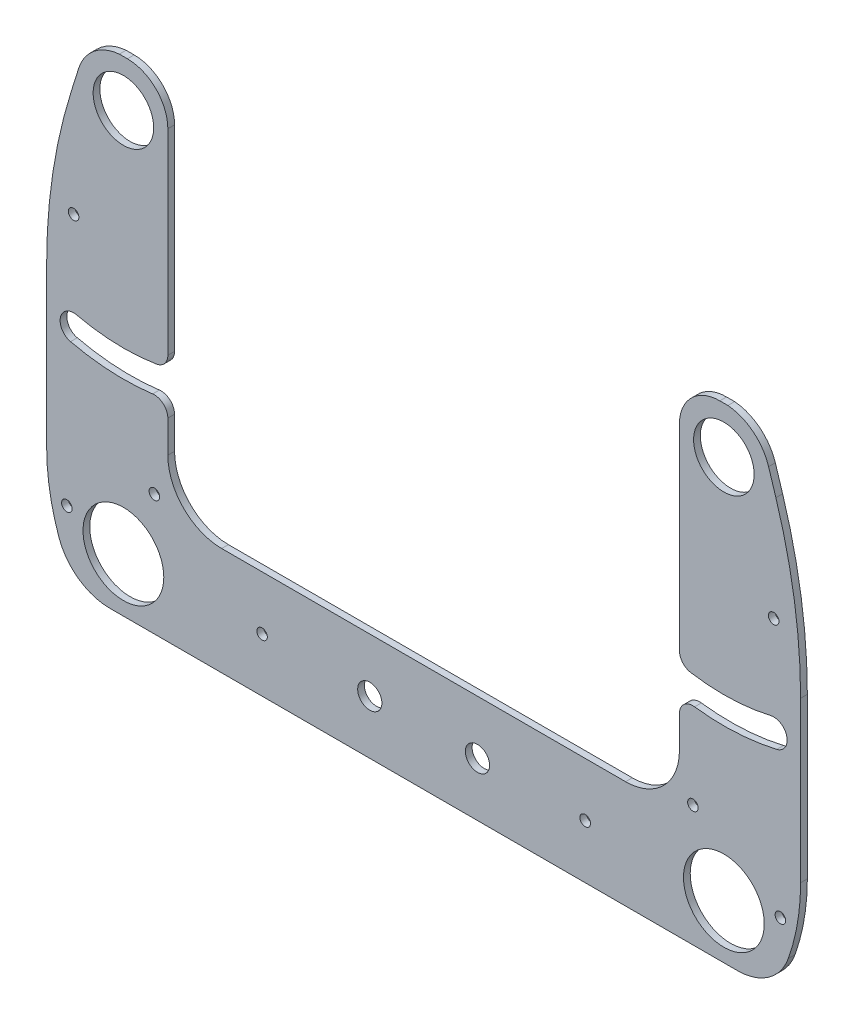
SolidWorks part; units mm, degrees
material "6061 Alloy"
ref_plane "Front Plane" through (0, 0, 0) normal (0, 0, 1) x (1, 0, 0)
ref_plane "Top Plane" through (0, 0, 0) normal (0, 1, 0) x (1, 0, 0)
ref_plane "Right Plane" through (0, 0, 0) normal (1, 0, 0) x (0, 0, -1)
sketch "Sketch1" plane through (0, 0, 0) normal (0, 0, 1) x (1, 0, 0)
  line L5 (120.65, -152.4) -> (120.65, -6.35)
  line L6 (127, 0) -> (171.45, 0) construction
  line L7 (177.8, -6.35) -> (177.8, -222.25)
  line L10 (0, -206.2199) -> (0, -63.6275) construction
  line L11 (-54.9244, 0) -> (300.6756, 0) construction
  line L13 (12.7, -177.8) -> (95.25, -177.8)
  line L14 (12.7, -228.6) -> (171.45, -228.6)
  line L15 (141.605, -22.0269) -> (141.605, -80.9091) construction
  line L16 (141.605, -22.0269) -> (141.605, -123.6269) construction
  line L19 (-141.605, -19.05) -> (-141.605, -77.9322) construction
  line L20 (141.605, -22.0269) -> (141.605, -203.2) construction
  line L22 (-120.65, -152.4) -> (-120.65, -6.35)
  line L23 (-12.7, -177.8) -> (-95.25, -177.8)
  line L24 (-12.7, -228.6) -> (-171.45, -228.6)
  line L25 (-177.8, -6.35) -> (-177.8, -222.25)
  line L26 (-12.7, -177.8) -> (12.7, -177.8)
  line L27 (-12.7, -228.6) -> (12.7, -228.6)
  line L28 (-177.8, -6.35) -> (-177.8, 6.35)
  line L29 (-165.1, 19.05) -> (-133.35, 19.05)
  line L30 (-120.65, 6.35) -> (-120.65, -6.35)
  line L31 (120.65, 6.35) -> (120.65, -6.35)
  line L32 (177.8, -6.35) -> (177.8, 6.35)
  line L33 (165.1, 19.05) -> (133.35, 19.05)
  arc A0 (95.25, -177.8) -> (120.65, -152.4) centre (95.25, -152.4) ccw
  arc A4 (120.65, -6.35) -> (127, 0) centre (127, -6.35) cw construction
  circle A8 centre (141.605, -22.0269) radius 14.2875
  circle A9 centre (141.605, -22.0269) radius 38.1 construction
  arc A10 (177.8, -6.35) -> (171.45, 0) centre (171.45, -6.35) ccw construction
  arc A11 (171.45, -228.6) -> (177.8, -222.25) centre (171.45, -222.25) ccw
  arc A14 (141.605, -79.1769) -> (120.9214, -75.3027) centre (141.605, -22.0269) ccw construction
  arc A15 (-141.605, -79.1769) -> (-120.9214, -75.3027) centre (-141.605, -22.0269) cw construction
  circle A16 centre (-141.605, -22.0269) radius 38.1 construction
  circle A17 centre (-141.605, -22.0269) radius 14.2875
  arc A19 (-95.25, -177.8) -> (-120.65, -152.4) centre (-95.25, -152.4) cw
  circle A20 centre (141.605, -123.6269) radius 38.1 construction
  circle A21 centre (-141.605, -123.6269) radius 38.1 construction
  arc A23 (-171.45, -228.6) -> (-177.8, -222.25) centre (-171.45, -222.25) cw
  circle A24 centre (-141.605, -203.2) radius 19.05
  circle A37 centre (141.605, -203.2) radius 19.05
  circle A39 centre (-76.2, -203.2) radius 2.4892
  circle A40 centre (76.2, -203.2) radius 2.4892
  circle A42 centre (-25.4, -203.2) radius 5.715
  arc A44 (-133.35, 19.05) -> (-120.65, 6.35) centre (-133.35, 6.35) cw
  arc A45 (-177.8, 6.35) -> (-165.1, 19.05) centre (-165.1, 6.35) cw
  arc A46 (133.35, 19.05) -> (120.65, 6.35) centre (133.35, 6.35) ccw
  arc A47 (177.8, 6.35) -> (165.1, 19.05) centre (165.1, 6.35) ccw
  circle A50 centre (-149.225, 6.35) radius 2.4892
  circle A53 centre (149.225, 6.35) radius 2.4892
  circle A54 centre (-168.275, -196.85) radius 2.4892
  circle A56 centre (168.275, -196.85) radius 2.4892
  circle A58 centre (-165.1, -76.2) radius 2.4892
  circle A59 centre (165.1, -76.2) radius 2.4892
  circle A60 centre (-127, -171.45) radius 2.4892
  circle A61 centre (127, -171.45) radius 2.4892
  circle A62 centre (25.4, -203.2) radius 5.715
  point P2 (177.8, -44.45)
  point P18 (177.8, 0)
  point P23 (177.8, -228.6)
  point P24 (177.8, -228.6)
  point P31 (177.8, 0)
  point P48 (-177.8, 0)
  point P49 (-177.8, -228.6)
  point P51 (-177.8, -44.45)
  point P78 (-141.605, -203.2)
  dimension "D6" = 25.4
  dimension "D7" = 6.35
  dimension "D8" = 6.35
  dimension "D9" = 177.8
  dimension "D10" = 28.575
  dimension "D12" = 76.2
  dimension "D13" = 57.15
  dimension "D15" = 38.1
  dimension "D18" = 76.2
  dimension "D21" = 4.9784
  dimension "D29" = 9.525
  dimension "D32" = 4.9784
  dimension "D35" = 11.43
  dimension "D40" = 12.7
  dimension "D43" = 4.9784
  dimension "D45" = 12.7
  dimension "D30" = 4.9784
  dimension "D41" = 4.9784
  dimension "D22" = 6.35
  dimension "D2" = 120.65
  dimension "D3" = 177.8
  dimension "D4" = 228.6
  dimension "D5" = 177.8
  dimension "D11" = 20.955
  dimension "`" = 22.0269
  dimension "D14" = 57.15
  dimension "D16" = 184.15
  dimension "D17" = 101.6
  dimension "D19" = 25.4
  dimension "D20" = 101.6
  dimension "D23" = 57.15
  dimension "D25" = 25.4
  dimension "D26" = 31.75
  dimension "D27" = 25.4
  dimension "D28" = 25.4
  dimension "D31" = 25.4
  dimension "D33" = 12.7
  dimension "D34" = 25.4
  dimension "D39" = 19.05
  dimension "D44" = 28.575
  dimension "D24" = 95.25
extrude "Boss-Extrude3" add sketch "Sketch1" along normal blind 3.175
sketch "Sketch2" plane through (0, 0, 3.175) normal (0, 0, 1) x (1, 0, 0)
  line L0 (177.8, -222.25) -> (177.8, 6.35) construction
  line L1 (-177.8, 19.05) -> (177.8, 19.05)
  line L2 (-177.8, 19.05) -> (-177.8, 0)
  line L3 (-177.8, 0) -> (177.8, 0)
  line L4 (177.8, 19.05) -> (177.8, 0)
  line L5 (-177.8, 6.35) -> (-177.8, -222.25) construction
  line L7 (-133.35, 19.05) -> (-165.1, 19.05) construction
  dimension "D1" = 19.05
extrude "Cut-Extrude1" cut sketch "Sketch2" against normal through all
fillet "Fillet1" radius 19.05 4 edges at (177.8, 0, 1.5875) (120.65, 0, 1.5875) (-120.65, 0, 1.5875) (-177.8, 0, 1.5875)
sketch "Sketch3" plane through (0, 0, 3.175) normal (0, 0, 1) x (1, 0, 0)
  line L2 (-177.8, -19.05) -> (-177.8, -222.25) construction
  line L3 (-158.75, 0) -> (-139.7, 0) construction
  line L4 (-177.8, -63.5) -> (-177.8, 0)
  line L5 (-177.8, 0) -> (-139.7, 0)
  line L6 (-177.8, -63.5) -> (-162.6988, -15.4039)
  arc A3 (-139.7, 0) -> (-162.6988, -15.4039) centre (-141.605, -22.0269) ccw
  arc M14 (-158.75, 0) -> (-177.8, -19.05) centre (-158.75, -19.05) ccw
  line M15 (-177.8, -19.05) -> (-177.8, -222.25)
  dimension "D1" = 63.5
extrude "Cut-Extrude2" cut sketch "Sketch3" against normal through all contours A3 L5 M14 M15 | L5 L4 M14 region at (-169.5998, -21.9282, 3.175) region at (-173.5448, -4.2552, 3.175)
ref_plane "Plane1" through (0, 0, 0) normal (-1, 0, 0) x (0, 0, 1)
mirror "Mirror1" about plane through (0, 0, 0) normal (-1, 0, 0) of "Cut-Extrude2"
fillet "Fillet2" radius 254 2 edges at (177.8, -63.5, 1.5875) (-177.8, -63.5, 1.5875)
sketch "Sketch4" plane through (0, 0, 3.175) normal (0, 0, 1) x (1, 0, 0)
  line L0 (0, -177.8) -> (0, -13.685) construction
  line L5 (-177.8, -102.4383) -> (-177.8, -222.25) construction
  line L6 (-171.45, -228.6) -> (171.45, -228.6) construction
  line L7 (-177.8, -177.8) -> (-177.8, -228.6)
  line L8 (-177.8, -228.6) -> (-164.1882, -228.6)
  line L9 (177.8, -177.8) -> (177.8, -228.6)
  line L10 (177.8, -228.6) -> (164.1882, -228.6)
  circle A0 centre (-76.2, -177.8) radius 101.6 construction
  arc A1 (-177.8, -177.8) -> (-164.1882, -228.6) centre (-76.2, -177.8) ccw
  arc A2 (177.8, -177.8) -> (164.1882, -228.6) centre (76.2, -177.8) cw
  dimension "D1" = 203.2
  dimension "D2" = 50.8
extrude "Cut-Extrude3" cut sketch "Sketch4" against normal through all contours L8 A1 L7 | L9 L10 A2
fillet "Fillet3" radius 25.4 2 edges at (164.1882, -228.6, 1.5875) (-164.1882, -228.6, 1.5875)
sketch "Sketch5" plane through (0, 0, 3.175) normal (0, 0, 1) x (1, 0, 0)
  line L2 (-120.65, -129.7962) -> (-120.65, -116.8262)
  line L5 (120.65, -129.7962) -> (120.65, -116.8262)
  line L6 (120.65, -19.05) -> (120.65, -152.4) construction
  line L7 (177.8, -177.8) -> (177.8, -102.4383) construction
  line L8 (0, -203.7675) -> (0, -15.567) construction
  circle A4 centre (141.605, -22.0269) radius 103.4377 construction
  arc A5 (120.65, -116.8262) -> (163.6577, -116.5769) centre (141.605, -22.0269) ccw
  arc A6 (120.65, -129.7962) -> (166.5423, -128.9449) centre (141.605, -22.0269) ccw
  arc A9 (166.5423, -128.9449) -> (163.6577, -116.5769) centre (165.1, -122.7609) ccw
  arc A10 (-120.65, -129.7962) -> (-166.5423, -128.9449) centre (-141.605, -22.0269) cw
  arc A11 (-120.65, -116.8262) -> (-163.6577, -116.5769) centre (-141.605, -22.0269) cw
  arc A12 (-166.5423, -128.9449) -> (-163.6577, -116.5769) centre (-165.1, -122.7609) cw
  dimension "D1" = 97.0877
  dimension "D2" = 109.7877
  dimension "D4" = 12.7
  dimension "D3" = 206.8754
extrude "Cut-Extrude4" cut sketch "Sketch5" against normal through all contours A10 A12 A11 L2 | A9 A5 L5 A6
fillet "Fillet4" radius 6.35 4 edges at (120.65, -129.7962, 1.5875) (120.65, -116.8262, 1.5875) (-120.65, -129.7962, 1.5875) (-120.65, -116.8262, 1.5875)
